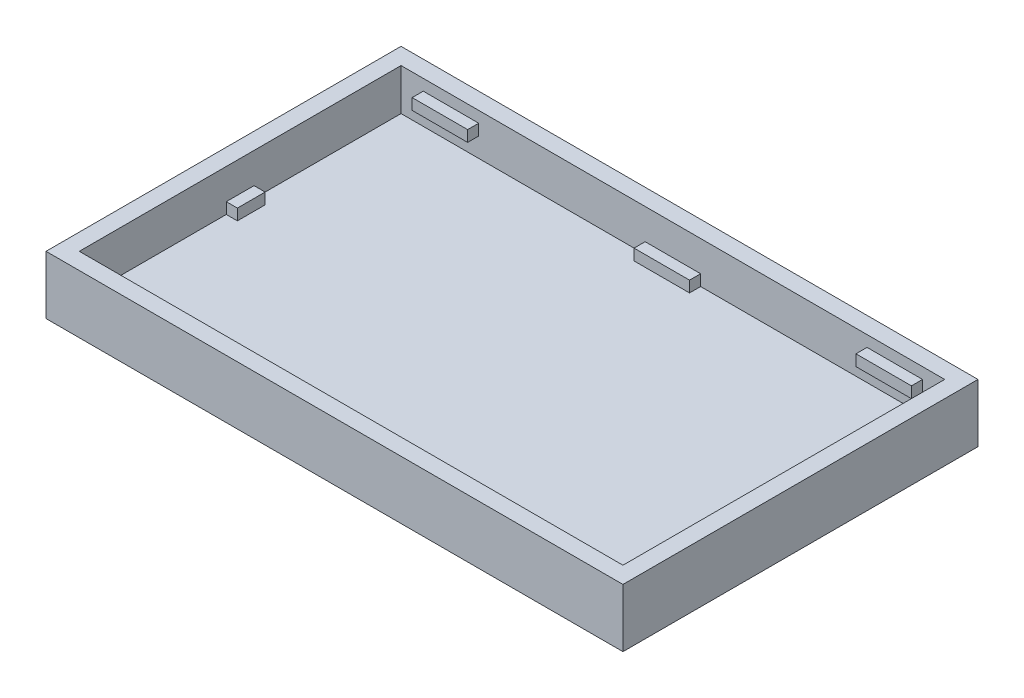
SolidWorks part; units mm, degrees
ref_plane "前视基准面" through (0, 0, 0) normal (0, 0, 1) x (1, 0, 0)
ref_plane "上视基准面" through (0, 0, 0) normal (0, 1, 0) x (1, 0, 0)
ref_plane "右视基准面" through (0, 0, 0) normal (1, 0, 0) x (0, 0, -1)
other "Configuration Table"
sketch "草图1" plane through (0, 0, 0) normal (0, 1, 0) x (1, 0, 0)
  line L1 (-42, -25) -> (42, -25)
  line L2 (-45, -22) -> (-45, 22)
  line L3 (-42, 25) -> (42, 25)
  line L4 (45, -22) -> (45, 22)
  line L5 (-45, -25) -> (45, 25) construction
  line L6 (-45, 25) -> (45, -25) construction
  line L7 (-49, 29) -> (49, 29)
  line L8 (-49, 29) -> (-49, -29)
  line L9 (-49, -29) -> (49, -29)
  line L10 (49, 29) -> (49, -29)
  line L11 (-52, 32) -> (52, 32)
  line L12 (-52, 32) -> (-52, -32)
  line L13 (-52, -32) -> (52, -32)
  line L14 (52, 32) -> (52, -32)
  arc A0 (-42, -25) -> (-45, -22) centre (-42, -22) cw
  arc A1 (45, -22) -> (42, -25) centre (42, -22) cw
  arc A2 (45, 22) -> (42, 25) centre (42, 22) ccw
  arc A3 (-45, 22) -> (-42, 25) centre (-42, 22) cw
  circle A4 centre (-39, 19) radius 1.5
  circle A5 centre (39, 19) radius 1.5
  circle A6 centre (-39, -19) radius 1.5
  circle A7 centre (39, -19) radius 1.5
  point P0 (0, 0)
  dimension "D3" = 3
  dimension "D4" = 3
  dimension "D1" = 90
  dimension "D2" = 50
  dimension "D5" = 6
  dimension "D6" = 6
  dimension "D7" = 6
  dimension "D8" = 6
  dimension "D9" = 4
  dimension "D10" = 4
  dimension "D11" = 4
  dimension "D12" = 4
  dimension "D13" = 3
  dimension "D14" = 3
  dimension "D15" = 3
  dimension "D16" = 3
extrude "凸台-拉伸1" add sketch "草图1" along normal blind 2 contours L12 L13 L14 L11 | L8 L9 L10 L7
extrude "凸台-拉伸2" add sketch "草图1<3>" against normal blind 3 contours L13 L14 L11 L12
sketch "草图1<3>" plane through (0, 0, 0) normal (0, 1, 0) x (1, 0, 0) same geometry as "草图1"
sketch "草图2" plane through (0, 0, 0) normal (0, 1, 0) x (1, 0, 0)
  line L0 (-49, 29) -> (-49, -29) construction
  line L1 (-49, 2.5) -> (-47, 2.5)
  line L2 (-49, 2.5) -> (-49, -2.5)
  line L3 (-49, -2.5) -> (-47, -2.5)
  line L4 (-47, 2.5) -> (-47, -2.5)
  line L5 (49, 29) -> (49, -29) construction
  line L6 (49, 2.5) -> (47, 2.5)
  line L7 (49, 2.5) -> (49, -2.5)
  line L8 (49, -2.5) -> (47, -2.5)
  line L9 (47, 2.5) -> (47, -2.5)
  line L10 (-49, 29) -> (49, 29) construction
  line L11 (-5, 29) -> (5, 29)
  line L12 (-5, 29) -> (-5, 27)
  line L13 (-5, 27) -> (5, 27)
  line L14 (5, 29) -> (5, 27)
  line L15 (-49, -29) -> (49, -29) construction
  line L16 (-5, -29) -> (5, -29)
  line L17 (-5, -29) -> (-5, -27)
  line L18 (-5, -27) -> (5, -27)
  line L19 (5, -29) -> (5, -27)
  line L20 (-47, 0) -> (47, 0)
  line L21 (0, 27) -> (0, -27)
  dimension "D1" = 2
  dimension "D2" = 5
  dimension "D3" = 10
extrude "凸台-拉伸3" add sketch "草图2" along normal up to surface (2 mm away) contours L3 L4 L1 L2 | L13 L14 L11 L12 | L16 L19 L18 L17 | L8 L9 L6 L7 up to face at (0, 2, 0)
extrude "凸台-拉伸4" add sketch "草图1<4>" along normal blind 3.5 from surface contours L13 L14 L11 L12 | L8 L9 L10 L7 starting at face at (0, 2, 0)
sketch "草图1<4>" plane through (0, 0, 0) normal (0, 1, 0) x (1, 0, 0) same geometry as "草图1"
sketch "草图3" plane through (0, 5.5, 0) normal (0, 1, 0) x (1, 0, 0)
  line L0 (-49, -29) -> (49, -29) construction
  line L1 (45, -29) -> (35, -29)
  line L2 (45, -29) -> (45, -27)
  line L3 (45, -27) -> (35, -27)
  line L4 (35, -29) -> (35, -27)
  line L5 (-49, 29) -> (49, 29) construction
  line L6 (-45, -29) -> (-35, -29)
  line L7 (-45, -29) -> (-45, -27)
  line L8 (-45, -27) -> (-35, -27)
  line L9 (-35, -29) -> (-35, -27)
  line L10 (45, 29) -> (35, 29)
  line L11 (45, 29) -> (45, 27)
  line L12 (45, 27) -> (35, 27)
  line L13 (35, 29) -> (35, 27)
  line L14 (-49, 29) -> (-49, -29) construction
  line L15 (-35, 29) -> (-45, 29)
  line L16 (-35, 29) -> (-35, 27)
  line L17 (-35, 27) -> (-45, 27)
  line L18 (-45, 29) -> (-45, 27)
  line L19 (49, 29) -> (49, -29) construction
  point P24 (0, 0)
  dimension "D1" = 4
  dimension "D2" = 4
  dimension "D3" = 2
  dimension "D4" = 2
  dimension "D5" = 10
extrude "凸台-拉伸5" add sketch "草图3" against normal blind 2
extrude "凸台-拉伸6" add sketch "草图1<5>" along normal blind 2 from surface contours L14 L13 L12 L11 | L9 L10 L7 L8 starting at face at (0, 5.5, 0)
sketch "草图1<5>" plane through (0, 0, 0) normal (0, 1, 0) x (1, 0, 0) same geometry as "草图1"
